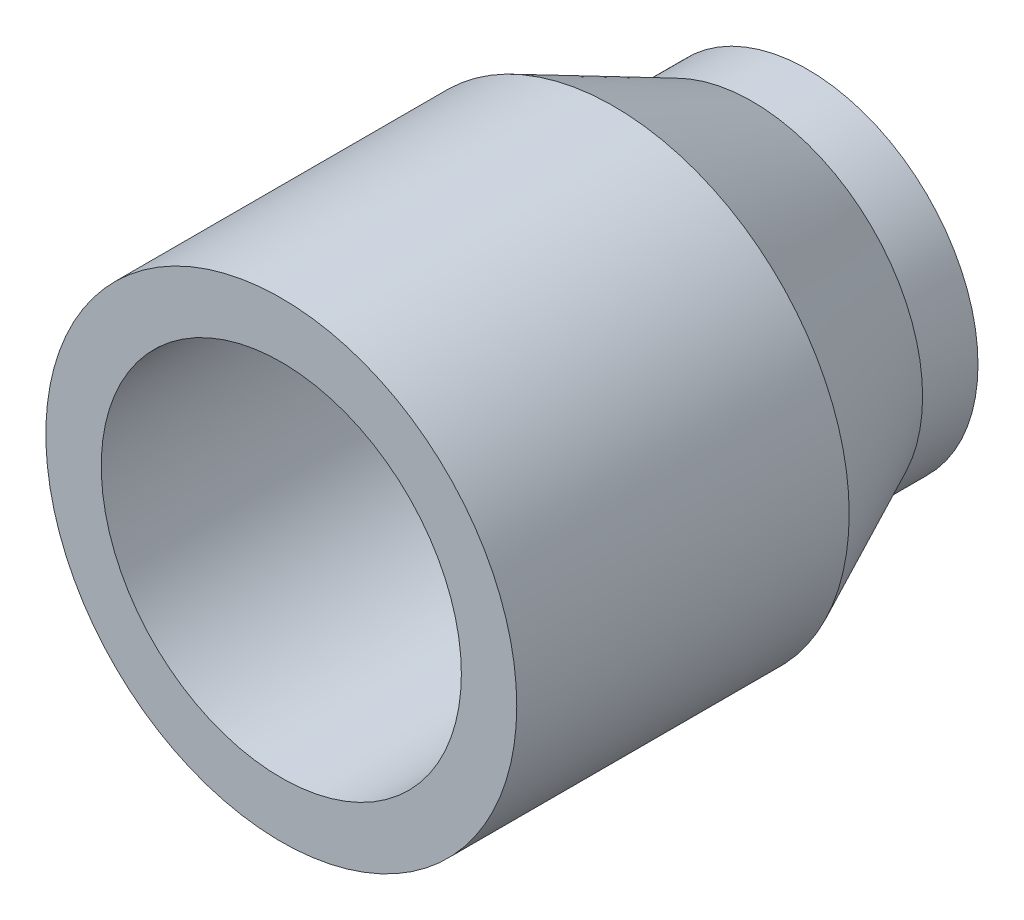
SolidWorks part; units mm, degrees
ref_plane "Front Plane" through (0, 0, 0) normal (0, 0, 1) x (1, 0, 0)
ref_plane "Top Plane" through (0, 0, 0) normal (0, 1, 0) x (1, 0, 0)
ref_plane "Right Plane" through (0, 0, 0) normal (1, 0, 0) x (0, 0, -1)
sketch "Sketch1" plane through (0, 0, 0) normal (0, 0, 1) x (1, 0, 0)
  circle A0 centre (0, 0) radius 4.15
  circle A1 centre (0, 0) radius 6.15
  dimension "D1" = 8.3
  dimension "D2" = 2
ref_plane "Plane1" through (0, 0, 5) normal (0, 0, 1) x (1, 0, 0)
sketch "Sketch2" plane through (0, 0, 5) normal (0, 0, 1) x (1, 0, 0)
  circle A0 centre (0, 0) radius 6.5
  circle A1 centre (0, 0) radius 8.5
  point P0 (0, 0)
  dimension "D1" = 13
  dimension "D2" = 2
loft "Loft1" add section "Sketch1" section "Sketch2" connector at (-5.1705, 3.3299, 0) connector at (-7.0926, 4.6845, 5)
loft "Cut-Loft1" cut section "Sketch1<3>" section "Sketch2<3>" connector at (-1.9124, -3.6831, 0) connector at (-3.1849, -5.6662, 5)
sketch "Sketch1<3>" plane through (0, 0, 0) normal (0, 0, 1) x (1, 0, 0) same geometry as "Sketch1"
sketch "Sketch2<3>" plane through (0, 0, 5) normal (0, 0, 1) x (1, 0, 0) same geometry as "Sketch2"
extrude "Boss-Extrude1" add sketch "Sketch1<4>" against normal blind 2
sketch "Sketch1<4>" plane through (0, 0, 0) normal (0, 0, 1) x (1, 0, 0) same geometry as "Sketch1"
extrude "Boss-Extrude2" add sketch "Sketch2<4>" along normal blind 12
sketch "Sketch2<4>" plane through (0, 0, 5) normal (0, 0, 1) x (1, 0, 0) same geometry as "Sketch2"
